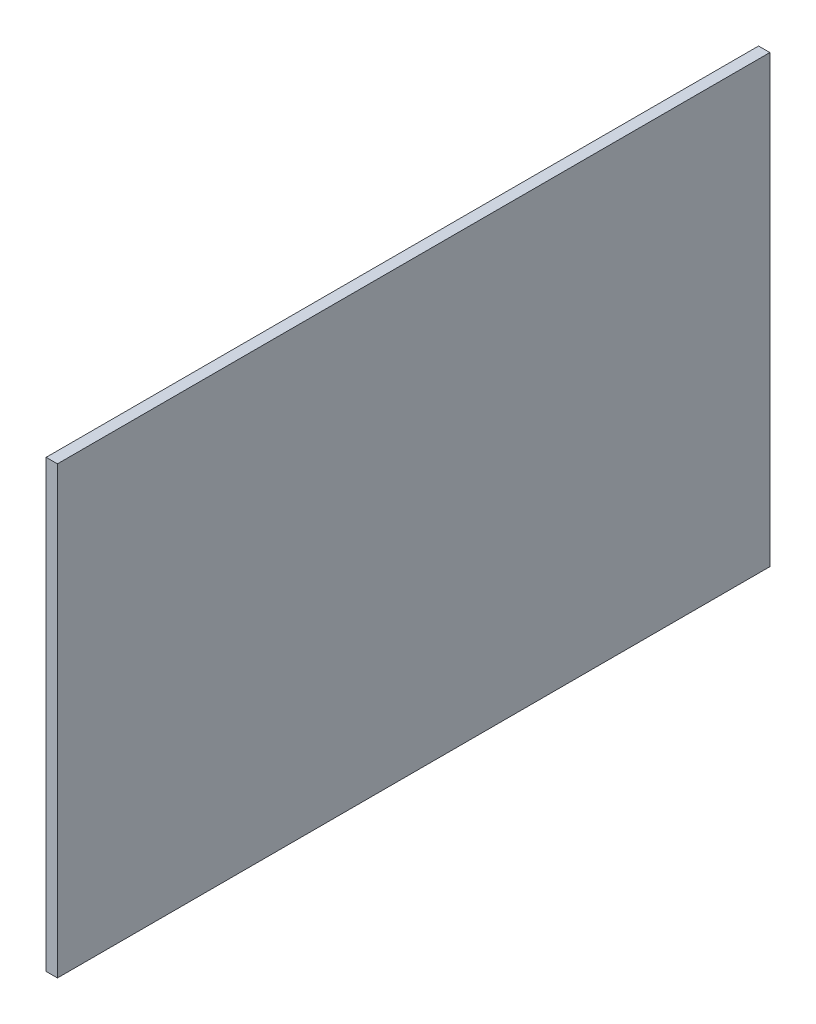
SolidWorks part; units mm, degrees
ref_plane "Front Plane" through (0, 0, 0) normal (0, 0, 1) x (1, 0, 0)
ref_plane "Top Plane" through (0, 0, 0) normal (0, 1, 0) x (1, 0, 0)
ref_plane "Right Plane" through (0, 0, 0) normal (1, 0, 0) x (0, 0, -1)
sketch "Sketch1" plane through (0, 0, 0) normal (1, 0, 0) x (0, 0, -1)
  line L1 (-79.9973, 49.9999) -> (79.9973, 49.9999)
  line L2 (-79.9973, 49.9999) -> (-79.9973, -49.9999)
  line L3 (-79.9973, -49.9999) -> (79.9973, -49.9999)
  line L4 (79.9973, 49.9999) -> (79.9973, -49.9999)
  line L5 (-79.9973, 49.9999) -> (79.9973, -49.9999) construction
  line L6 (-79.9973, -49.9999) -> (79.9973, 49.9999) construction
  point P0 (0, 0)
  dimension "D1" = 99.9998
  dimension "D2" = 159.9946
extrude "Boss-Extrude1" add sketch "Sketch1" along normal mid plane 2.54
ref_axis "Axis1" through (1.27, 0, 79.9973) along (0, 0, -1)
